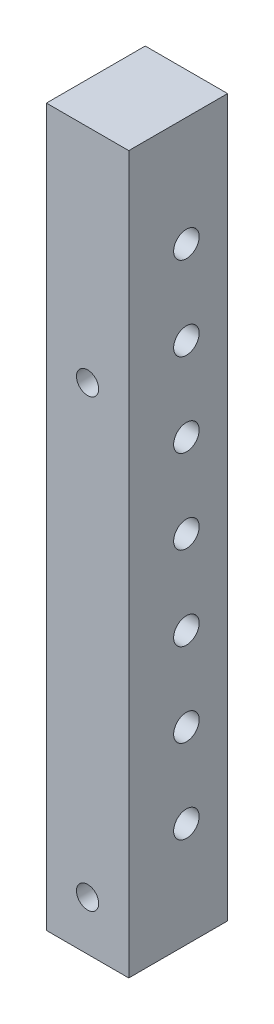
SolidWorks part; units mm, degrees
ref_plane "前基準面" through (0, 0, 0) normal (0, 0, 1) x (1, 0, 0)
ref_plane "上基準面" through (0, 0, 0) normal (0, 1, 0) x (1, 0, 0)
ref_plane "右基準面" through (0, 0, 0) normal (1, 0, 0) x (0, 0, -1)
sketch "草圖1" plane through (0, 0, 0) normal (0, 1, 0) x (1, 0, 0)
  line L1 (-5, 6) -> (5, 6)
  line L2 (-5, 6) -> (-5, -6)
  line L3 (-5, -6) -> (5, -6)
  line L4 (5, 6) -> (5, -6)
  line L5 (-5, 6) -> (5, -6) construction
  line L6 (-5, -6) -> (5, 6) construction
  point P0 (0, 0)
  dimension "D1" = 12
  dimension "D2" = 10
extrude "填料-伸長1" add sketch "草圖1" along normal blind 87
sketch "草圖5" plane through (0, 87, 0) normal (0, 1, 0) x (1, 0, 0)
  point P0 (0, 0)
sketch "草圖8" plane through (-5, 0, 0) normal (-1, 0, 0) x (0, 0, 1)
  line L0 (-6, 87) -> (-6, 0) construction
  line L1 (55, 0) -> (-55, 0) construction
  line L2 (-1, 12.73) -> (-1, 33.05) construction
  point P0 (-1, 12.73)
  point P5 (-1, 73.69)
  point P6 (-1, 33.05)
  point P8 (-1, 53.37)
  dimension "D1" = 5
  dimension "D2" = 12.73
  dimension "D4" = 20.32
  dimension "D3" = 4
hole_wizard "Ø3.1 (3.1) 直徑孔1" positions "3D草圖5" profile "草圖9" hole size "Ø3.1" standard "GB" end condition through all
sketch3d "3D草圖5"
  point P0 (-5, 53.37, -1)
  point P3 (-5, 33.05, -1)
  point P6 (-5, 12.73, -1)
  point P9 (-5, 73.69, -1)
sketch "草圖9" plane through (-5, 53.37, -1) normal (0, 1, 0) x (0, 0, 1)
  line L0 (0, 0) -> (0, 10)
  line L1 (0, 10) -> (1.55, 10)
  line L2 (1.55, 10) -> (1.55, 0)
  line L5 (1.55, 0) -> (0, 0)
  line L11 (0, -6.35) -> (0, 107.95) construction
  dimension "貫穿孔直徑" = 3.1
  dimension "貫穿孔深度" = 10
sketch "草圖10" plane through (0, 0, -6) normal (0, 0, -1) x (-1, 0, 0)
  line L1 (5, 87) -> (5, 0) construction
  line L2 (5.5, 0) -> (-5.5, 0) construction
  point P0 (0, 60.1)
  point P1 (0, 6)
  dimension "D1" = 60.1
  dimension "D2" = 5
  dimension "D3" = 5
  dimension "D4" = 6
hole_wizard "Ø2.7 (2.7) 直徑孔1" positions "3D草圖6" profile "草圖11" hole size "Ø2.7" standard "GB" end condition through all
sketch3d "3D草圖6"
  point P0 (0, 60.1, -6)
  point P3 (0, 6, -6)
sketch "草圖11" plane through (0, 60.1, -6) normal (1, 0, 0) x (0, 1, 0)
  line L0 (0, 0) -> (0, 12)
  line L1 (0, 12) -> (1.35, 12)
  line L2 (1.35, 12) -> (1.35, 0)
  line L5 (1.35, 0) -> (0, 0)
  line L11 (0, -6.35) -> (0, 107.95) construction
  dimension "貫穿孔直徑" = 2.7
  dimension "貫穿孔深度" = 12
sketch "草圖12" plane through (-5, 0, 0) normal (-1, 0, 0) x (0, 0, 1)
  line L0 (-1, 12.73) -> (-1, 33.05) construction
  point P0 (-1, 22.89)
  point P2 (-1, 43.21)
  point P3 (-1, 63.53)
  dimension "D1" = 3
hole_wizard "Ø3.1 (3.1) 直徑孔2" positions "3D草圖7" profile "草圖13" hole size "Ø3.1" standard "GB" end condition through all
sketch3d "3D草圖7"
  point P0 (-5, 63.53, -1)
  point P3 (-5, 43.21, -1)
  point P6 (-5, 22.89, -1)
sketch "草圖13" plane through (-5, 63.53, -1) normal (0, 1, 0) x (0, 0, 1)
  line L0 (0, 0) -> (0, 10)
  line L1 (0, 10) -> (1.55, 10)
  line L2 (1.55, 10) -> (1.55, 0)
  line L5 (1.55, 0) -> (0, 0)
  line L11 (0, -6.35) -> (0, 107.95) construction
  dimension "貫穿孔直徑" = 3.1
  dimension "貫穿孔深度" = 10
